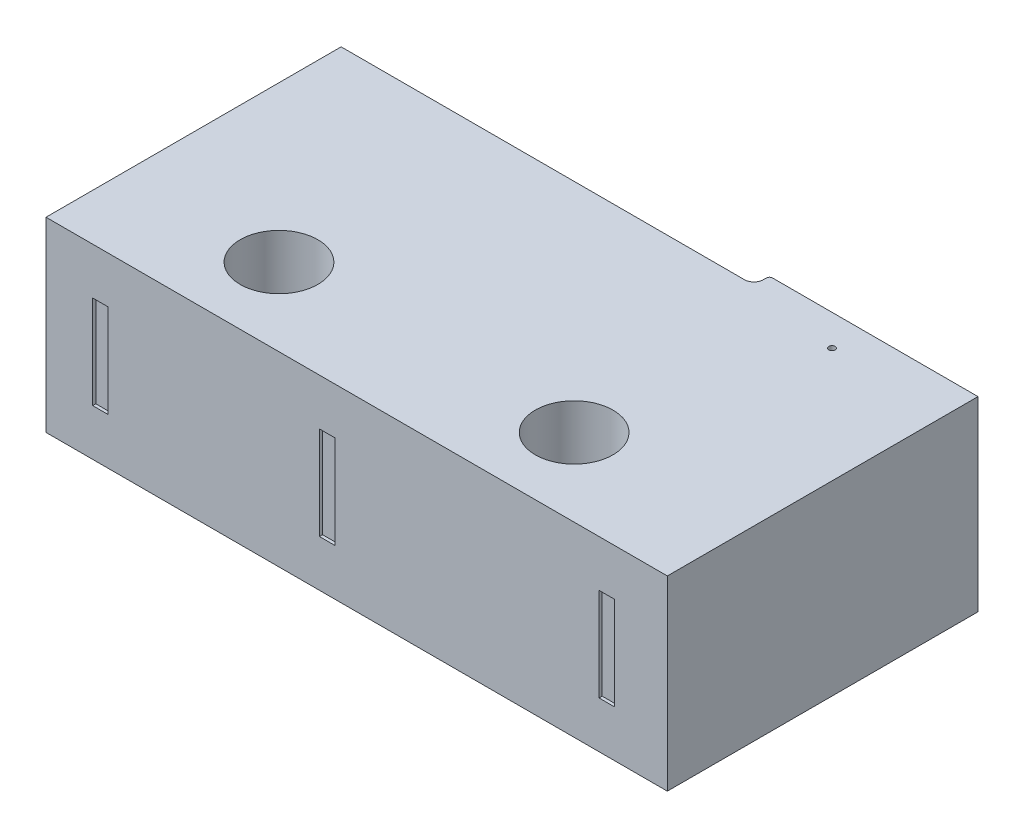
SolidWorks part; units mm, degrees
material "Plástico personalizado"
ref_plane "Alzado" through (0, 0, 0) normal (0, 0, 1) x (1, 0, 0)
ref_plane "Planta" through (0, 0, 0) normal (0, 1, 0) x (1, 0, 0)
ref_plane "Vista lateral" through (0, 0, 0) normal (1, 0, 0) x (0, 0, -1)
sketch "Croquis1" plane through (0, 0, 0) normal (0, 1, 0) x (1, 0, 0)
  line L0 (-10, 4.5) -> (-10, 5)
  line L1 (10, -5) -> (-10, -5)
  line L2 (10, -5) -> (10, 5)
  line L3 (10, 5) -> (-10, 5)
  line L4 (-10, -5) -> (-10, 5)
  line L5 (10, -5) -> (-10, 5) construction
  line L6 (10, 5) -> (-10, -5) construction
  line L7 (-10, 4.5) -> (2.9867, 4.5)
  line L8 (3.2867, 4.8) -> (3.2867, 5)
  line L9 (3.2867, 5) -> (10, 5)
  arc A0 (3.2867, 4.8) -> (2.9867, 4.5) centre (2.9867, 4.8) cw
  point P0 (0, 0)
  dimension "D4" = 0.3
  dimension "D1" = 10
  dimension "D2" = 20
  dimension "D3" = 0.5
extrude "Saliente-Extruir2" add sketch "Croquis1" along normal blind 6 contours L8 A0 L7 L4 L1 L2 L3 region at (0.1156, 0, 0.1627)
sketch "Croquis2" plane through (0, 6, 0) normal (0, 1, 0) x (1, 0, 0)
  line L3 (10, -5) -> (10, 5) construction
  circle A0 centre (-5, -2.5) radius 1.25
  circle A1 centre (4.5, -2.5) radius 1.25
  dimension "D1" = 2.5
  dimension "D2" = 2.5
  dimension "D3" = 9.5
  dimension "D4" = 5
  dimension "D5" = 5.5
extrude "Cortar-Extruir1" cut sketch "Croquis2" against normal blind 10
fillet "Redondeo1" radius 0.1 1 edges at (3.2867, 3, -5)
sketch "Croquis3" plane through (0, 0, -4.5) normal (0, 0, -1) x (-1, 0, 0)
  line L0 (-3.3867, 0) -> (-3.3867, 6) construction
  line L1 (0.6133, 1.35) -> (-1.3867, 1.35)
  line L2 (0.6133, 1.35) -> (0.6133, 4.65)
  line L3 (0.6133, 4.65) -> (-1.3867, 4.65)
  line L4 (-1.3867, 1.35) -> (-1.3867, 4.65)
  line L5 (0.6133, 1.35) -> (-1.3867, 4.65) construction
  line L6 (0.6133, 4.65) -> (-1.3867, 1.35) construction
  line L8 (10, 0) -> (-2.9867, 0) construction
  point P0 (-0.3867, 3)
  dimension "D1" = 2
  dimension "D2" = 2
  dimension "D3" = 3.3
  dimension "D4" = 3
extrude "Cortar-Extruir2" cut sketch "Croquis3" against normal blind 5
sketch "Croquis4" plane through (0, 6, 0) normal (0, 1, 0) x (1, 0, 0)
  line L0 (10, 4) -> (6.3, 4)
  line L1 (10, -5) -> (10, 5) construction
  line L2 (10, 5) -> (10, 4)
  circle A0 centre (6.3, 4) radius 0.1
  dimension "D3" = 0.2
  dimension "D1" = 3.7
  dimension "D2" = 1
extrude "Cortar-Extruir3" cut sketch "Croquis4" against normal up to surface (6 mm away) contours A0 region at (6.2028, 6, -4) up to face at (-5, 0, 3.75)
sketch "Croquis5" plane through (0, 0, 5) normal (0, 0, 1) x (1, 0, 0)
  line L0 (-10, 3) -> (10, 3) construction
  line L1 (-10, 6) -> (-10, 0) construction
  line L2 (10, 6) -> (10, 0) construction
  line L4 (-7.9972, 1.5) -> (-8.4972, 1.5)
  line L5 (-7.9972, 1.5) -> (-7.9972, 4.5)
  line L6 (-7.9972, 4.5) -> (-8.4972, 4.5)
  line L7 (-8.4972, 1.5) -> (-8.4972, 4.5)
  line L8 (-7.9972, 1.5) -> (-8.4972, 4.5) construction
  line L9 (-7.9972, 4.5) -> (-8.4972, 1.5) construction
  line L10 (-0.6972, 1.5) -> (-1.1972, 1.5)
  line L11 (-0.6972, 1.5) -> (-0.6972, 4.5)
  line L12 (-0.6972, 4.5) -> (-1.1972, 4.5)
  line L13 (-1.1972, 1.5) -> (-1.1972, 4.5)
  line L14 (-0.6972, 1.5) -> (-1.1972, 4.5) construction
  line L15 (-0.6972, 4.5) -> (-1.1972, 1.5) construction
  line L16 (8.3028, 1.5) -> (7.8028, 1.5)
  line L17 (8.3028, 1.5) -> (8.3028, 4.5)
  line L18 (8.3028, 4.5) -> (7.8028, 4.5)
  line L19 (7.8028, 1.5) -> (7.8028, 4.5)
  line L20 (8.3028, 1.5) -> (7.8028, 4.5) construction
  line L21 (8.3028, 4.5) -> (7.8028, 1.5) construction
  point P6 (-8.2472, 3)
  point P11 (-0.9472, 3)
  point P16 (8.0528, 3)
  dimension "D1" = 0.5
  dimension "D2" = 0.5
  dimension "D3" = 0.5
  dimension "D4" = 3
  dimension "D5" = 3
  dimension "D6" = 3
  dimension "D7" = 7.8
  dimension "D8" = 9.5
extrude "Cortar-Extruir4" cut sketch "Croquis5" against normal blind 0.1
